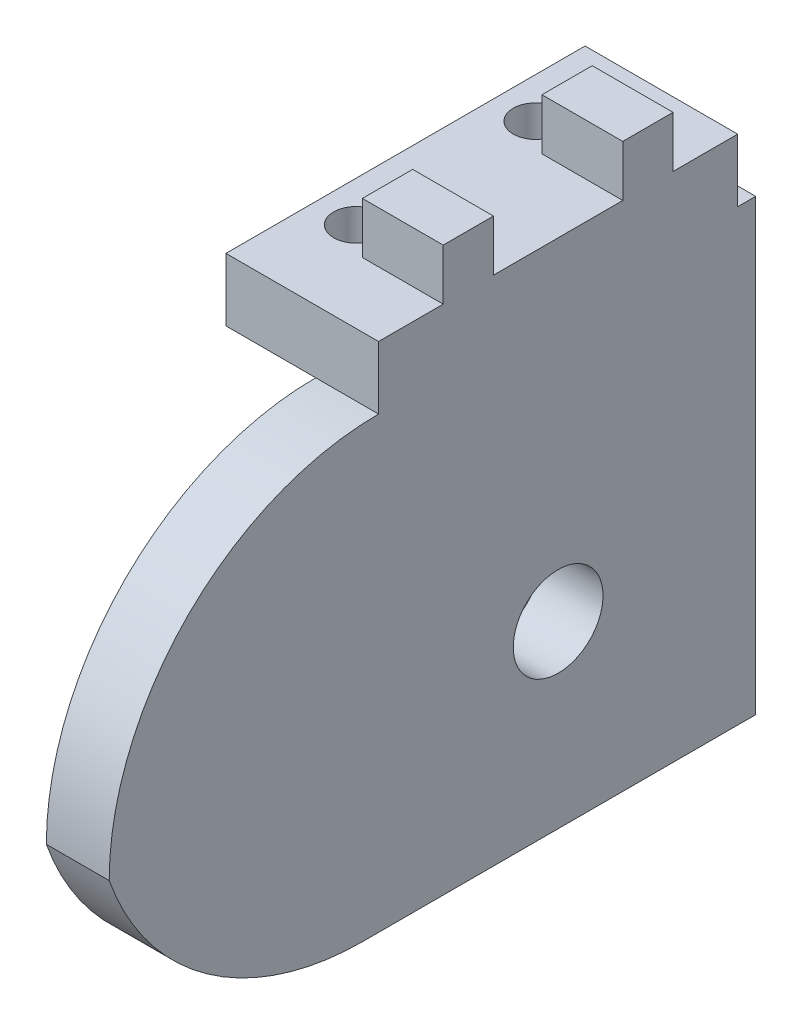
SolidWorks part; units mm, degrees
ref_plane "Alzado" through (0, 0, 0) normal (0, 0, 1) x (1, 0, 0)
ref_plane "Planta" through (0, 0, 0) normal (0, 1, 0) x (1, 0, 0)
ref_plane "Vista lateral" through (0, 0, 0) normal (1, 0, 0) x (0, 0, -1)
sketch "Croquis1" plane through (0, 0, 0) normal (0, 1, 0) x (1, 0, 0)
  line L1 (20, 20) -> (-20, 20)
  line L2 (20, 20) -> (20, -20)
  line L3 (20, -20) -> (-20, -20)
  line L4 (-20, 20) -> (-20, -20)
  line L5 (20, 20) -> (-20, -20) construction
  line L6 (20, -20) -> (-20, 20) construction
  point P0 (0, 0)
  dimension "D1" = 40
  dimension "D2" = 40
extrude "Saliente-Extruir1" add sketch "Croquis1" along normal blind 7
sketch "Croquis3" plane through (-20, 0, 0) normal (-1, 0, 0) x (0, 0, 1)
  line L0 (-20, 7) -> (20, 7) construction
  line L5 (-12.8, 12.7) -> (-7.2, 7) construction
  line L6 (7.2, 7) -> (12.8, 7)
  line L7 (7.2, 7) -> (7.2, 12.7)
  line L8 (7.2, 12.7) -> (12.8, 12.7)
  line L9 (12.8, 7) -> (12.8, 12.7)
  line L12 (-7.2, 7) -> (-12.8, 7)
  line L13 (-7.2, 7) -> (-7.2, 12.7)
  line L14 (-7.2, 12.7) -> (-12.8, 12.7)
  line L15 (-12.8, 7) -> (-12.8, 12.7)
  line L16 (-7.2, 12.7) -> (-12.8, 7) construction
  line L17 (7.2, 12.7) -> (12.8, 7) construction
  line L18 (12.8, 12.7) -> (7.2, 7) construction
  point P10 (-10, 9.85)
  point P11 (10, 9.85)
  dimension "D1" = 10
  dimension "D2" = 10
  dimension "D3" = 5.6
  dimension "D4" = 5.6
  dimension "D5" = 5.7
extrude "Saliente-Extruir3" add sketch "Croquis3" against normal up to surface (40 mm away) up to face at (20, 3.5, 0)
sketch "Croquis19" plane through (0, 12.7, 0) normal (0, 1, 0) x (1, 0, 0)
  line L0 (20, 20) -> (-20, 20) construction
  line L1 (-12, 20) -> (-20, 20)
  line L2 (-12, 20) -> (-12, -20)
  line L3 (-12, -20) -> (-20, -20)
  line L4 (-20, 20) -> (-20, -20)
  line L5 (-12, 20) -> (-20, -20) construction
  line L6 (-12, -20) -> (-20, 20) construction
  line L7 (20, 20) -> (12, 20)
  line L8 (20, 20) -> (20, -20)
  line L9 (20, -20) -> (12, -20)
  line L10 (12, 20) -> (12, -20)
  line L11 (20, 20) -> (12, -20) construction
  line L12 (20, -20) -> (12, 20) construction
  line L13 (-20, -20) -> (20, -20) construction
  line L16 (20, -7.2) -> (20, 7.2) construction
  line L17 (-20, 7.2) -> (-20, -7.2) construction
  point P0 (-16, 0)
  point P5 (16, 0)
  dimension "D1" = 8
  dimension "D4" = 8
extrude "Cortar-Extruir5" cut sketch "Croquis19" against normal up to surface (5.7 mm away) up to face at (0, 7, 0)
sketch "Croquis20" plane through (0, 7, 0) normal (0, 1, 0) x (1, 0, 0)
  line L0 (15.5, 16.9883) -> (15.5, -23.2433) construction
  line L3 (20, 20) -> (-20, 20) construction
  line L4 (-20, -20) -> (20, -20) construction
  line L5 (-15.5, 16.9883) -> (-15.5, -23.2433) construction
  line L6 (20, -20) -> (20, 20) construction
  line L7 (-20, 20) -> (-20, -20) construction
  circle A0 centre (-15.5, 10) radius 2.5
  circle A1 centre (15.5, 10) radius 2.5
  circle A2 centre (15.5, -10) radius 2.5
  circle A3 centre (-15.5, -10) radius 2.5
  dimension "D1" = 5
  dimension "D2" = 10
  dimension "D3" = 10
  dimension "D4" = 4.5
  dimension "D5" = 4.5
extrude "Cortar-Extruir6" cut sketch "Croquis20" against normal up to surface (7 mm away) up to face at (0, 0, 0)
sketch "Croquis21" plane through (0, 0, 0) normal (0, -1, 0) x (1, 0, 0)
  line L0 (-20, 20) -> (20, 20) construction
  line L9 (-20, -20) -> (-20, 20) construction
  line L10 (-3, 50) -> (-10, 50)
  line L11 (-3, 50) -> (-3, -22)
  line L12 (-3, -22) -> (-10, -22)
  line L13 (-10, 50) -> (-10, -22)
  line L14 (-3, 50) -> (-10, -22) construction
  line L15 (-3, -22) -> (-10, 50) construction
  point P0 (0, 0)
  point P1 (-6.5, 14)
  dimension "D1" = 7
  dimension "D2" = 72
  dimension "D3" = 30
  dimension "D4" = 10
extrude "Saliente-Extruir4" add sketch "Croquis21" along normal blind 50
sketch "Croquis22" plane through (-3, 0, 0) normal (1, 0, 0) x (0, 0, -1)
  line L0 (20, 0) -> (-20, 0) construction
  line L1 (22, -50) -> (-50, -50) construction
  circle A0 centre (0, -30) radius 5
  point P5 (0, 0)
  dimension "D1" = 10
  dimension "D2" = 20
extrude "Cortar-Extruir7" cut sketch "Croquis22" against normal up to surface (7 mm away) up to face at (-10, -16.6667, 9.3333)
fillet "Redondeo1" radius 30 1 edges at (-6.5, 0, 50)
fillet "Redondeo2" radius 30 1 edges at (-6.5, -50, 50)
sketch "Croquis28" plane through (-10, 0, 0) normal (-1, 0, 0) x (0, 0, 1)
  circle A0 centre (30, -30) radius 4.25
  circle A3 centre (0, -30) radius 6.5441 construction
  dimension "D1" = 8.5
  dimension "D2" = 30
extrude "Cortar-Extruir11" cut sketch "Croquis28" against normal blind 3
sketch "Croquis29" plane through (20, 0, 0) normal (1, 0, 0) x (0, 0, -1)
  line L1 (56.9544, 95.98) -> (-56.9544, 95.98)
  line L2 (56.9544, 95.98) -> (56.9544, -87.5846)
  line L3 (56.9544, -87.5846) -> (-56.9544, -87.5846)
  line L4 (-56.9544, 95.98) -> (-56.9544, -87.5846)
  line L5 (56.9544, 95.98) -> (-56.9544, -87.5846) construction
  line L6 (56.9544, -87.5846) -> (-56.9544, 95.98) construction
  point P0 (0, 4.1977)
extrude "Cortar-Extruir12" cut sketch "Croquis29" against normal up to surface (23 mm away) up to face at (-3, -30, -5)
